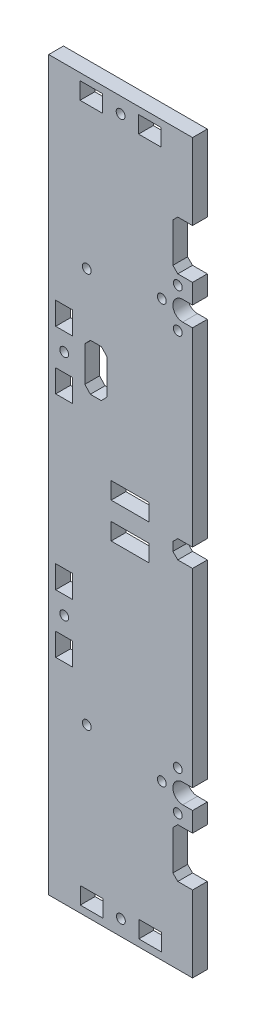
SolidWorks part; units mm, degrees
ref_plane "Plano frontal" through (0, 0, 0) normal (0, 0, 1) x (1, 0, 0)
ref_plane "Plano superior" through (0, 0, 0) normal (0, 1, 0) x (1, 0, 0)
ref_plane "Plano direito" through (0, 0, 0) normal (1, 0, 0) x (0, 0, -1)
sketch "Model" plane through (0, 0, 0) normal (0, 0, 1) x (1, 0, 0)
  line L0 (89.7713, 6.2321) -> (31.2713, 6.2321)
  line L1 (89.7713, 302.232) -> (89.7713, 271.232)
  line L2 (81.7713, 39.2321) -> (81.7713, 55.2321)
  line L3 (89.7713, 57.2321) -> (83.7713, 57.2321)
  line L4 (83.7713, 271.232) -> (89.7713, 271.232)
  line L5 (89.7713, 251.232) -> (89.7713, 243.232)
  line L6 (83.7713, 271.232) -> (81.7713, 269.232)
  line L7 (83.7713, 251.232) -> (89.7713, 251.232)
  line L8 (89.7713, 37.2321) -> (83.7713, 37.2321)
  line L9 (89.7713, 235.232) -> (89.7713, 157.982)
  line L10 (85.7713, 65.2321) -> (89.7713, 65.2321)
  line L11 (81.7713, 253.232) -> (81.7713, 269.232)
  line L12 (83.7713, 57.2321) -> (81.7713, 55.2321)
  line L13 (89.7713, 65.2321) -> (89.7713, 57.2321)
  line L14 (31.2713, 6.2321) -> (31.2713, 302.232)
  line L15 (85.7713, 243.232) -> (89.7713, 243.232)
  line L16 (31.2713, 302.232) -> (89.7713, 302.232)
  line L17 (83.7713, 37.2321) -> (81.7713, 39.2321)
  line L18 (85.7713, 235.232) -> (89.7713, 235.232)
  line L19 (85.7713, 73.2321) -> (89.7713, 73.2321)
  line L20 (89.7713, 37.2321) -> (89.7713, 6.2321)
  line L21 (83.7713, 251.232) -> (81.7713, 253.232)
  line L22 (77.1213, 9.0821) -> (77.1213, 15.9821)
  line L23 (44.0213, 299.382) -> (44.0213, 292.482)
  line L24 (72.0713, 143.582) -> (56.6713, 143.582)
  line L25 (41.0213, 91.332) -> (41.0213, 100.532)
  line L26 (53.2213, 292.482) -> (53.2213, 299.382)
  line L27 (77.0213, 299.382) -> (67.8213, 299.382)
  line L28 (77.0213, 292.482) -> (77.0213, 299.382)
  line L29 (34.1213, 217.132) -> (34.1213, 207.932)
  line L30 (34.1213, 115.132) -> (41.0213, 115.132)
  line L31 (41.0213, 207.932) -> (41.0213, 217.132)
  line L32 (44.0213, 292.482) -> (53.2213, 292.482)
  line L33 (34.1213, 91.332) -> (41.0213, 91.332)
  line L34 (44.1213, 15.9821) -> (44.1213, 9.0821)
  line L35 (34.1213, 184.132) -> (41.0213, 184.132)
  line L36 (53.2213, 299.382) -> (44.0213, 299.382)
  line L37 (41.0213, 193.332) -> (34.1213, 193.332)
  line L38 (34.1213, 124.332) -> (34.1213, 115.132)
  line L39 (41.0213, 100.532) -> (34.1213, 100.532)
  line L40 (56.6713, 157.982) -> (56.6713, 164.882)
  line L41 (53.3213, 15.9821) -> (44.1213, 15.9821)
  line L42 (41.0213, 115.132) -> (41.0213, 124.332)
  line L43 (34.1213, 100.532) -> (34.1213, 91.332)
  line L44 (77.1213, 15.9821) -> (67.9213, 15.9821)
  line L45 (72.0713, 164.882) -> (72.0713, 157.982)
  line L46 (53.3213, 9.0821) -> (53.3213, 15.9821)
  line L47 (67.8213, 299.382) -> (67.8213, 292.482)
  line L48 (72.0713, 157.982) -> (56.6713, 157.982)
  line L49 (67.9213, 9.0821) -> (77.1213, 9.0821)
  line L50 (67.8213, 292.482) -> (77.0213, 292.482)
  line L51 (41.0213, 184.132) -> (41.0213, 193.332)
  line L52 (44.1213, 9.0821) -> (53.3213, 9.0821)
  line L53 (34.1213, 207.932) -> (41.0213, 207.932)
  line L54 (56.6713, 164.882) -> (72.0713, 164.882)
  line L55 (34.1213, 193.332) -> (34.1213, 184.132)
  line L56 (67.9213, 15.9821) -> (67.9213, 9.0821)
  line L57 (56.6713, 143.582) -> (56.6713, 150.482)
  line L58 (56.6713, 150.482) -> (72.0713, 150.482)
  line L59 (72.0713, 150.482) -> (72.0713, 143.582)
  line L60 (41.0213, 217.132) -> (34.1213, 217.132)
  line L61 (41.0213, 124.332) -> (34.1213, 124.332)
  line L62 (54.9192, 207.6856) -> (52.6792, 210.0656)
  line L63 (52.6792, 191.0304) -> (48.1992, 191.0304)
  line L64 (52.6792, 191.0304) -> (54.9192, 193.4104)
  line L65 (45.9592, 193.4104) -> (48.1992, 191.0304)
  line L66 (45.9592, 207.6856) -> (45.9592, 193.4104)
  line L67 (48.1992, 210.0656) -> (45.9592, 207.6856)
  line L68 (48.1992, 210.0656) -> (52.6792, 210.0656)
  line L69 (54.9192, 207.6856) -> (54.9192, 193.4104)
  line L70 (83.7713, 157.982) -> (81.7713, 155.982)
  line L71 (83.7713, 150.482) -> (81.7713, 152.482)
  line L72 (81.7713, 152.482) -> (81.7713, 155.982)
  line L73 (89.7713, 157.982) -> (83.7713, 157.982)
  line L74 (89.7713, 150.482) -> (83.7713, 150.482)
  line L75 (89.7713, 150.482) -> (89.7713, 73.2321)
  circle A0 centre (60.6213, 12.5321) radius 1.8
  circle A1 centre (83.7713, 61.2332) radius 1.8
  circle A2 centre (77.2713, 69.2321) radius 1.8
  circle A3 centre (83.7713, 77.232) radius 1.8
  circle A4 centre (46.7713, 73.882) radius 1.8
  circle A5 centre (37.5713, 107.832) radius 1.8
  circle A6 centre (37.5713, 200.632) radius 1.8
  circle A7 centre (46.7713, 234.582) radius 1.8
  circle A8 centre (83.7713, 231.2331) radius 1.8
  circle A9 centre (77.2713, 239.232) radius 1.8
  circle A10 centre (83.7713, 247.232) radius 1.8
  circle A11 centre (60.5213, 295.932) radius 1.8
  arc A12 (85.7713, 243.232) -> (85.7713, 235.232) centre (85.7713, 239.232) ccw
  arc A13 (85.7713, 73.2321) -> (85.7713, 65.2321) centre (85.7713, 69.2321) ccw
extrude "Ressalto-extrusão1" add sketch "Model" along normal blind 6
ref_plane "Plano1" through (60.5713, 0, 0) normal (1, 0, 0) x (0, 0, -1)
